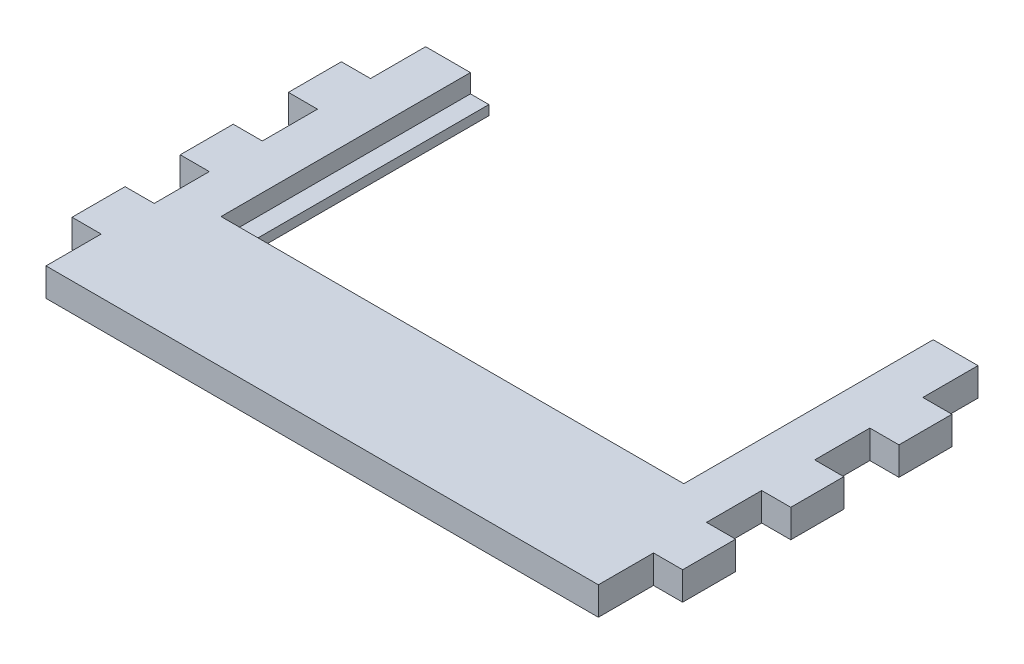
SolidWorks part; units mm, degrees
ref_plane "Plan de face" through (0, 0, 0) normal (0, 0, 1) x (1, 0, 0)
ref_plane "Plan de dessus" through (0, 0, 0) normal (0, 1, 0) x (1, 0, 0)
ref_plane "Plan de droite" through (0, 0, 0) normal (1, 0, 0) x (0, 0, -1)
sketch "Esquisse1" plane through (0, 0, 0) normal (0, 1, 0) x (1, 0, 0)
  line L1 (-163.0852, 185.3139) -> (167.4148, 185.3139)
  line L2 (-163.0852, 185.3139) -> (-163.0852, -20.1861)
  line L3 (-163.0852, -20.1861) -> (167.4148, -20.1861)
  line L4 (167.4148, 185.3139) -> (167.4148, -20.1861)
  line L5 (-113.0852, 185.3139) -> (117.4148, 185.3139)
  line L6 (-113.0852, 185.3139) -> (-113.0852, 60.3139)
  line L7 (-113.0852, 60.3139) -> (117.4148, 60.3139)
  line L8 (117.4148, 185.3139) -> (117.4148, 60.3139)
  dimension "D1" = 330.5
  dimension "D2" = 205.5
  dimension "D3" = 50
  dimension "D4" = 50
  dimension "D5" = 80.5
extrude "Boss.-Extru.1" add sketch "Esquisse1" along normal blind 15.25 contours L1 L8 L7 L6 L2 L3 L4 region at (2.1648, 0, -52.9079)
sketch "Esquisse2" plane through (0, 15.25, 0) normal (0, 1, 0) x (1, 0, 0)
  line L0 (-163.0852, 185.3139) -> (-113.0852, 185.3139) construction
  line L1 (-123.0852, 185.3139) -> (127.4148, 185.3139)
  line L2 (-123.0852, 185.3139) -> (-123.0852, 50.3139)
  line L3 (-123.0852, 50.3139) -> (127.4148, 50.3139)
  line L4 (127.4148, 185.3139) -> (127.4148, 50.3139)
  line L5 (2.1648, -20.1861) -> (2.1648, 185.3139) construction
  line L6 (-163.0852, -20.1861) -> (167.4148, -20.1861) construction
  line L8 (-113.0852, 185.3139) -> (-113.0852, 60.3139) construction
  line L9 (-113.0852, 60.3139) -> (117.4148, 60.3139) construction
  dimension "D1" = 10
  dimension "D2" = 10
extrude "Enlèv. mat.-Extru.1" cut sketch "Esquisse2" against normal blind 10
sketch "Esquisse3" plane through (0, 15.25, 0) normal (0, 1, 0) x (1, 0, 0)
  line L0 (-163.0852, 185.3139) -> (-163.0852, -20.1861) construction
  line L1 (-163.0852, 185.3139) -> (-147.3352, 185.3139)
  line L2 (-163.0852, 185.3139) -> (-163.0852, 155.4567)
  line L3 (-163.0852, 155.4567) -> (-147.3352, 155.4567)
  line L4 (-147.3352, 185.3139) -> (-147.3352, 155.4567)
  line L5 (-163.0852, 126.7662) -> (-147.3352, 126.7662)
  line L6 (-163.0852, 126.7662) -> (-163.0852, 96.9091)
  line L7 (-163.0852, 96.9091) -> (-147.3352, 96.9091)
  line L8 (-147.3352, 126.7662) -> (-147.3352, 96.9091)
  line L9 (-163.0852, -20.1861) -> (167.4148, -20.1861) construction
  line L10 (-163.0852, 68.2186) -> (-147.3352, 68.2186)
  line L11 (-163.0852, 68.2186) -> (-163.0852, 38.3615)
  line L12 (-163.0852, 38.3615) -> (-147.3352, 38.3615)
  line L13 (-147.3352, 68.2186) -> (-147.3352, 38.3615)
  line L14 (-163.0852, 9.671) -> (-147.3352, 9.671)
  line L15 (-163.0852, 9.671) -> (-163.0852, -20.1861)
  line L16 (-163.0852, -20.1861) -> (-147.3352, -20.1861)
  line L17 (-147.3352, 9.671) -> (-147.3352, -20.1861)
  line L18 (-163.0852, 9.671) -> (-163.0852, 38.3615) construction
  line L19 (-163.0852, 68.2186) -> (-163.0852, 96.9091) construction
  line L20 (-163.0852, 126.7662) -> (-163.0852, 155.4567) construction
  line L21 (-147.8352, 155.9567) -> (-147.8352, 185.3139) construction
  line L22 (-147.8352, 155.9567) -> (-163.0852, 155.9567) construction
  dimension "D1" = 0.5
  dimension "D2" = 0.5
extrude "Enlèv. mat.-Extru.2" cut sketch "Esquisse3" against normal up to next
ref_plane "Plan1" through (2.1648, 0, 0) normal (-1, 0, 0) x (0, 0, 1)
mirror "Symétrie1" about plane through (2.1648, 0, 0) normal (-1, 0, 0) of "Enlèv. mat.-Extru.2"
